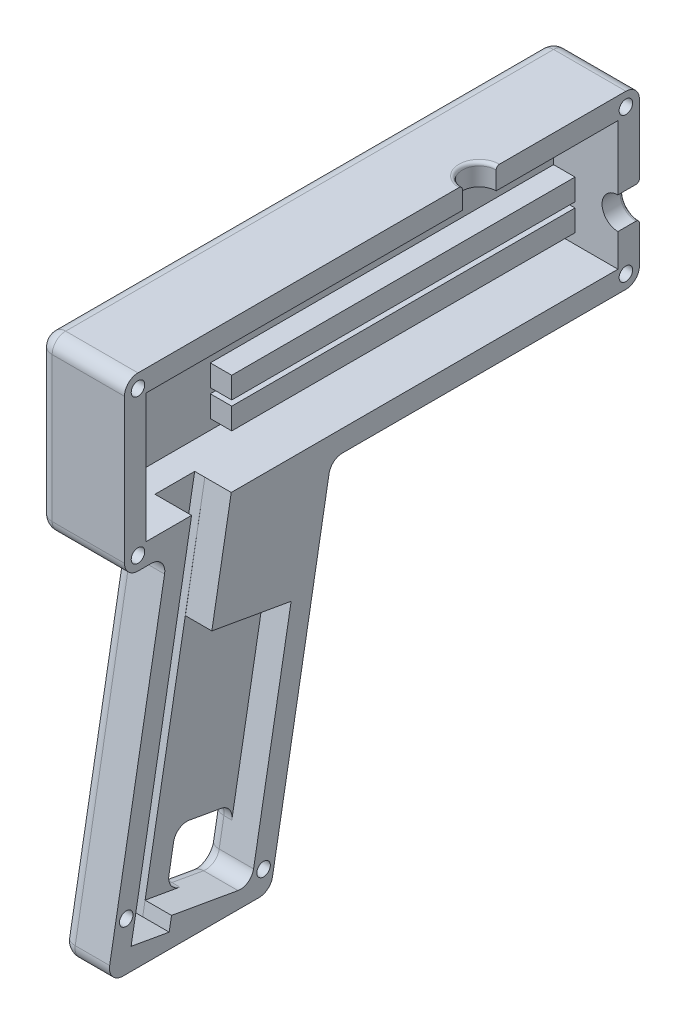
SolidWorks part; units mm, degrees
ref_plane "Front Plane" through (0, 0, 0) normal (0, 0, 1) x (1, 0, 0)
ref_plane "Top Plane" through (0, 0, 0) normal (0, 1, 0) x (1, 0, 0)
ref_plane "Right Plane" through (0, 0, 0) normal (1, 0, 0) x (0, 0, -1)
sketch "Sketch1" plane through (0, 0, 0) normal (0, 0, 1) x (1, 0, 0)
  line L1 (0, 0) -> (25.4, 0)
  line L2 (0, 0) -> (0, 50.8)
  line L3 (0, 50.8) -> (25.4, 50.8)
  line L4 (25.4, 0) -> (25.4, 50.8)
  dimension "D1" = 50.8
  dimension "D2" = 25.4
extrude "Boss-Extrude1" add sketch "Sketch1" against normal blind 152.4
sketch "Sketch2" plane through (25.4, 0, 0) normal (1, 0, 0) x (0, 0, -1)
  line L0 (0, 0) -> (0, 50.8) construction
  line L1 (6.35, 44.45) -> (146.05, 44.45)
  line L2 (6.35, 44.45) -> (6.35, 6.35)
  line L3 (6.35, 6.35) -> (146.05, 6.35)
  line L4 (146.05, 44.45) -> (146.05, 6.35)
  line L5 (152.4, 50.8) -> (0, 50.8) construction
  line L6 (152.4, 0) -> (0, 0) construction
  line L7 (152.4, 0) -> (152.4, 50.8) construction
  point P12 (6.35, 25.4)
  point P13 (0, 25.4)
  dimension "D1" = 6.35
  dimension "D2" = 6.35
  dimension "D3" = 6.35
  dimension "D4" = 6.35
extrude "Cut-Extrude1" cut sketch "Sketch2" against normal blind 19.05
sketch "Sketch4" plane through (0, 50.8, 0) normal (0, 1, 0) x (1, 0, 0)
  line L1 (25.4, 152.4) -> (25.4, 0) construction
  line L6 (0, 0) -> (25.4, 0)
  line L7 (25.4, 0) -> (25.4, 152.4)
  line L8 (25.4, 152.4) -> (0, 152.4)
  line L9 (0, 152.4) -> (0, 0)
  line L11 (25.4, 100) -> (25.4, 110)
  arc A1 (25.4, 100) -> (25.4, 110) centre (25.4, 105) cw
  dimension "D1" = 100
  dimension "D2" = 0
extrude "HitLED" cut sketch "Sketch4" against normal up to vertex (6.35 mm away) contours L11 A1 up to point (25.4, 44.45, -146.05)
sketch "Sketch5" plane through (6.35, 0, 0) normal (1, 0, 0) x (0, 0, -1)
  line L0 (44.45, 17.27) -> (146.05, 17.27)
  line L1 (44.45, 23.62) -> (146.05, 23.62)
  line L2 (44.45, 23.62) -> (44.45, 9.35)
  line L3 (44.45, 9.35) -> (146.05, 9.35)
  line L4 (146.05, 23.62) -> (146.05, 9.35)
  line L9 (44.45, 15.7) -> (146.05, 15.7)
  line L10 (6.35, 6.35) -> (146.05, 6.35) construction
  line L11 (146.05, 6.35) -> (146.05, 44.45) construction
  line M13 (146.05, 6.35) -> (146.05, 44.45)
  dimension "D1" = 1.57
  dimension "D2" = 6.35
  dimension "D3" = 6.35
  dimension "D4" = 3
  dimension "D5" = 0
  dimension "D6" = 101.6
extrude "PCB Slot" add sketch "Sketch5" along normal blind 6.35 contours L1 L2 L0 M13 | L9 L2 L3 M13 region at (6.35, 20.445, -95.25) region at (6.35, 12.525, -95.25)
sketch "Sketch7" plane through (0, 0, -146.05) normal (0, 0, 1) x (1, 0, 0)
  line L0 (25.4, 6.35) -> (25.4, 44.45) construction
  line L1 (25.4, 25.4) -> (25.4, 16)
  arc A0 (25.4, 16) -> (25.4, 25.4) centre (25.4, 20.7) cw
extrude "IRLED" cut sketch "Sketch7" against normal blind 6.35
sketch "Sketch8" plane through (25.4, 0, 25.4) normal (1, 0, 0) x (0, 0, -1)
  line L0 (38.1, 0) -> (20.1852, -101.6)
  line L1 (20.1852, -101.6) -> (68.621, -101.6)
  line L2 (68.621, -101.6) -> (86.5358, 0)
  line L4 (38.1, 0) -> (86.5358, 0)
  dimension "D1" = 12.7
  dimension "D3" = 47.7
extrude "Butt" add sketch "Sketch8" against normal blind 14.175
sketch "Sketch9" plane through (25.4, 0, 25.4) normal (1, 0, 0) x (0, 0, -1)
  line L7 (68.621, -101.6) -> (86.5358, 0) construction
  line L8 (51.2564, -26.2652) -> (74.7269, -30.4036)
  line L9 (28.0575, -91.2236) -> (62.9188, -97.3706)
  line L10 (74.7269, -30.4036) -> (62.9188, -97.3706)
  line L12 (31.75, 6.35) -> (171.45, 6.35) construction
  line L13 (45.2623, 6.35) -> (57.0073, 6.35)
  line L14 (57.0073, 6.35) -> (51.2564, -26.2652)
  line L15 (45.2623, 6.35) -> (28.0575, -91.2236)
  dimension "D3" = 68
  dimension "D4" = 3.175
extrude "BatteryPack" cut sketch "Sketch9" against normal blind 7.825
sketch "Sketch10" plane through (17.575, 0, 0) normal (1, 0, 0) x (0, 0, -1)
  line L0 (37.5188, -97.3706) -> (20.2847, -94.3317)
  line L1 (37.5188, -97.3706) -> (40.2972, -81.6136)
  line L2 (20.2847, -94.3317) -> (23.0631, -78.5748)
  line L3 (40.2972, -81.6136) -> (23.0631, -78.5748)
  line L4 (2.6575, -91.2236) -> (37.5188, -97.3706) construction
  dimension "D1" = 16
  dimension "D2" = 17.5
extrude "BatterySwitch" cut sketch "Sketch10" against normal up to next
sketch "Sketch11" plane through (0, -88.0184, 15.52) normal (0, 0.9848, -0.1736) x (1, 0, 0)
  line L0 (17.575, 18.4579) -> (25.4, 18.4579)
  line L1 (17.575, 18.4579) -> (17.575, 29.8992)
  line L2 (25.4, 18.4579) -> (25.4, 29.8992)
  line L3 (17.575, 29.8992) -> (25.4, 29.8992)
  dimension "D1" = 11.4413
extrude "WireSpace" cut sketch "Sketch11" against normal blind 4
sketch "Sketch12" plane through (17.575, 0, 0) normal (1, 0, 0) x (0, 0, -1)
  line L0 (19.8623, 6.35) -> (31.6073, 6.35)
  line L1 (31.6073, 6.35) -> (13.2303, -97.1496)
  line L2 (13.2303, -97.1496) -> (1.9629, -95.1628)
  line L3 (1.9629, -95.1628) -> (19.8623, 6.35)
extrude "WireRoute" cut sketch "Sketch12" against normal blind 3
fillet "Fillet-Body" radius 4 24 edges at (12.7, 0, -152.4) (18.3125, 0, -61.1358) (14.4, -78.5748, -23.0631) (14.4, -94.3317, -20.2847) (11.225, -89.4921, -38.908) (11.225, -95.8511, -28.9018) (11.225, -80.0942, -31.6801) (11.225, -86.4533, -21.6739) (18.3125, -97.3706, -37.5188) (14.4, -81.6136, -40.2972) (18.3125, -101.6, -43.221) (11.225, -101.6, -19.0031) (18.3125, -101.6, 5.2148) (0, 25.4, -152.4) (0, 0, -76.2) (11.225, -50.8, -52.1784) (11.225, -50.8, -3.7426) (11.225, 0, -36.9179) (18.3125, 0, -12.7) (12.7, 0, 0) (0, 25.4, 0) (12.7, 50.8, -152.4) (0, 50.8, -76.2) (12.7, 50.8, 0)
fillet "Fillet-LEDs" radius 1 2 edges at (20.4, 50.8, -105) (20.7, 20.7, -152.4)
sketch "Sketch13" plane through (25.4, 0, 0) normal (1, 0, 0) x (0, 0, -1)
  line L0 (99, 50.8) -> (4, 50.8) construction
  line L1 (0, 4) -> (0, 46.8) construction
  line L2 (7.933, 0) -> (4, 0) construction
  line L3 (152.4, 26.4) -> (152.4, 46.8) construction
  line L8 (49.3269, -30.4036) -> (25.8564, -26.2652) construction
  line L9 (43.8039, -98.2946) -> (60.553, -3.3054) construction
  line L10 (11.8722, -4.6946) -> (-4.387, -96.9054) construction
  circle A0 centre (4, 46.8) radius 2
  circle A1 centre (148.4, 46.8) radius 2
  circle A2 centre (148.4, 4) radius 2
  circle A3 centre (4, 4) radius 2
  circle A5 centre (0.5231, -87.3425) radius 2
  circle A6 centre (41.1665, -94.9675) radius 2
  dimension "D1" = 4
  dimension "D5" = 64.5486
  dimension "D2" = 4
  dimension "D3" = 4
  dimension "D4" = 4
  dimension "D6" = 65
  dimension "D7" = 3.175
  dimension "D8" = 3.175
extrude "PressFit" cut sketch "Sketch13" against normal blind 5
